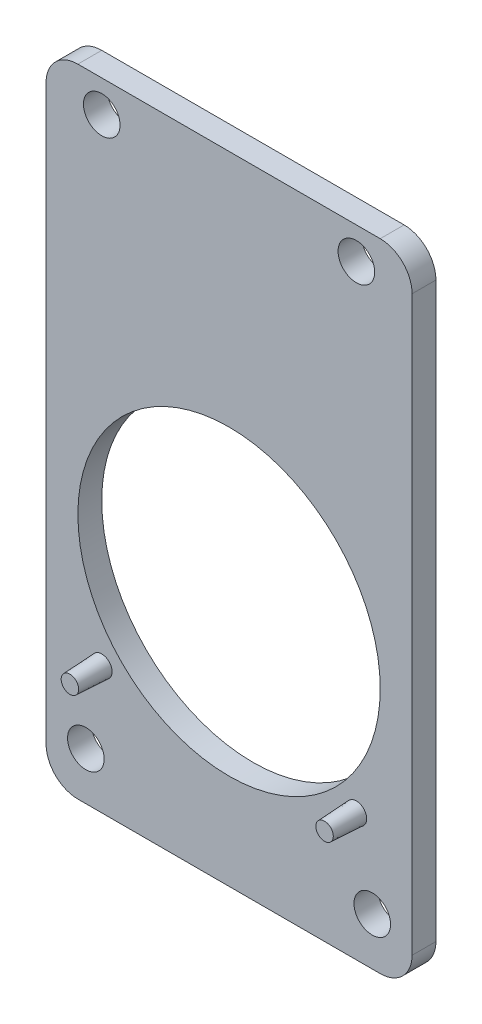
SolidWorks part; units mm, degrees
ref_plane "前视基准面" through (0, 0, 0) normal (0, 0, 1) x (1, 0, 0)
ref_plane "上视基准面" through (0, 0, 0) normal (0, 1, 0) x (1, 0, 0)
ref_plane "右视基准面" through (0, 0, 0) normal (1, 0, 0) x (0, 0, -1)
sketch "草图1" plane through (0, 0, 0) normal (0, 0, 1) x (1, 0, 0)
  line L0 (0, -4.5) -> (0, 11.0108) construction
  line L1 (-11.5, -20) -> (11.5, -20)
  line L2 (-11.5, -20) -> (-11.5, 20)
  line L3 (-11.5, 20) -> (11.5, 20)
  line L4 (11.5, -20) -> (11.5, 20)
  line L5 (-11.5, -20) -> (11.5, 20) construction
  line L6 (-11.5, 20) -> (11.5, -20) construction
  circle A0 centre (0, -4.5) radius 9.5
  point P0 (0, 0)
  dimension "D3" = 19
  dimension "D4" = 15.5
  dimension "D1" = 23
  dimension "D2" = 40
extrude "凸台-拉伸1" add sketch "草图1" along normal blind 1.5
fillet "圆角1" radius 2 4 edges at (-11.5, -20, 0.75) (11.5, -20, 0.75) (-11.5, 20, 0.75) (11.5, 20, 0.75)
sketch "草图3" plane through (0, 0, 1.5) normal (0, 0, 1) x (1, 0, 0)
  line L0 (0, 0) -> (0, 20.9871) construction
  line L1 (0, 0) -> (0, -21.9246) construction
  line L2 (9.5, 20) -> (-9.5, 20) construction
  line L3 (-9.5, -20) -> (9.5, -20) construction
  circle A0 centre (-8, 18) radius 1.15
  circle A1 centre (8, 18) radius 1.15
  circle A2 centre (-9, -17) radius 1.15
  circle A3 centre (9, -17) radius 1.15
  dimension "D1" = 2.3
  dimension "D2" = 2.3
  dimension "D4" = 3
  dimension "D6" = 18
  dimension "D3" = 2
  dimension "D5" = 16
extrude "切除-拉伸1" cut sketch "草图3" against normal through all
sketch "草图4" plane through (0, 0, 1.5) normal (0, 0, 1) x (1, 0, 0)
  line L0 (0, 0) -> (0, -9.2684) construction
  line L1 (-9.5, -20) -> (9.5, -20) construction
  circle A0 centre (-8, -12) radius 0.65
  circle A1 centre (8, -12) radius 0.65
  dimension "D1" = 1.3
  dimension "D2" = 8
  dimension "D3" = 8
extrude "凸台-拉伸2" add sketch "草图4" along normal blind 2
chamfer "倒角1" distance 2 distance2 0.1 2 edges at (8.65, -12, 3.5) (-7.35, -12, 3.5) first distance on face at (8.65, -12, 3.5) first distance on face at (-7.35, -12, 3.5)
